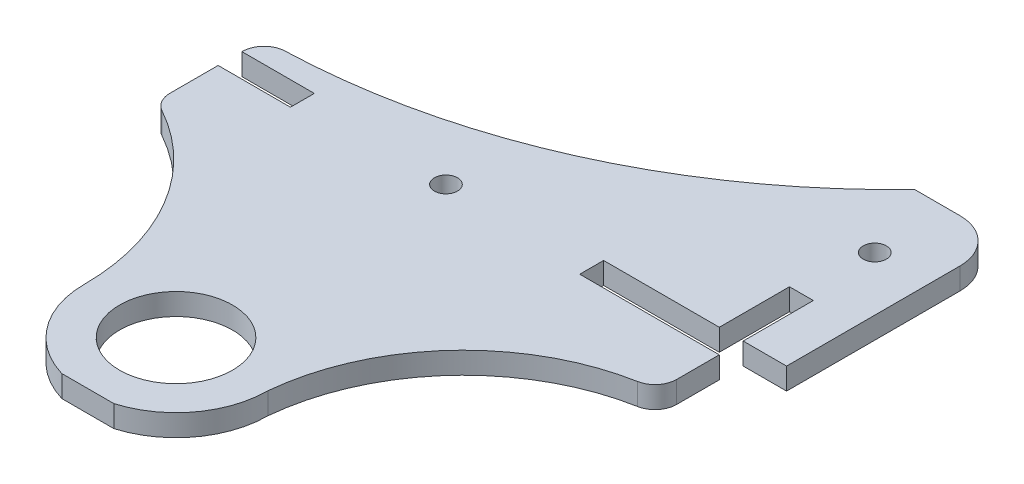
SolidWorks part; units mm, degrees
ref_plane "Alzado" through (0, 0, 0) normal (0, 0, 1) x (1, 0, 0)
ref_plane "Planta" through (0, 0, 0) normal (0, 1, 0) x (1, 0, 0)
ref_plane "Vista lateral" through (0, 0, 0) normal (1, 0, 0) x (0, 0, -1)
sketch "Croquis1" plane through (0, 0, 0) normal (0, 1, 0) x (1, 0, 0)
  line L0 (0, 38.7) -> (69.3, 38.7) construction
  line L1 (0, 0) -> (69.3, 0) construction
  line L2 (0, 0) -> (0, 38.7)
  line L3 (0, 72) -> (69.3, 72)
  line L4 (69.3, 0) -> (69.3, 38.7)
  line L5 (69.3, 51.7) -> (69.3, 72) construction
  line L8 (69.3, 51.7) -> (66, 51.7)
  line L9 (66, 42) -> (66, 51.7)
  line L11 (69.3, 38.7) -> (50, 38.7)
  line L13 (66, 42) -> (50, 42)
  line L14 (50, 38.7) -> (50, 42)
  line L15 (0, 38.7) -> (10, 38.7)
  line L17 (0, 42) -> (10, 42)
  line L18 (10, 38.7) -> (10, 42)
  line L19 (0, 42) -> (0, 72)
  line L20 (69.3, 72) -> (75.3, 72)
  line L21 (69.3, 72) -> (69.3, 51.7) construction
  line L23 (75.3, 72) -> (75.3, 52)
  line L25 (69.3, 51.7) -> (69.3, 42)
  line L26 (69.3, 42) -> (75.3, 42)
  line L27 (75.3, 52) -> (75.3, 42)
  line L28 (0, 0) -> (69.3, 0) construction
  line L29 (0, 0) -> (0, -9)
  line L30 (0, -9) -> (69.3, -9)
  line L31 (69.3, 0) -> (69.3, -9)
  circle A0 centre (30, 40.2) radius 1.6
  circle A1 centre (67.8, 61.7) radius 1.6
  circle A3 centre (29.68, 3.2) radius 7.8109
  dimension "D9" = 3.2
  dimension "D13" = 6
  dimension "D14" = 3.2
  dimension "D18" = 15.6218
  dimension "D2" = 72
  dimension "D3" = 3.3
  dimension "D4" = 13
  dimension "D5" = 16
  dimension "D6" = 3.3
  dimension "D7" = 3.3
  dimension "D8" = 10
  dimension "D10" = 30
  dimension "D11" = 20
  dimension "D12" = 1.5
  dimension "D15" = 1.5
  dimension "D16" = 10
  dimension "D17" = 40
  dimension "D19" = 35.5
  dimension "D20" = 29.68
  dimension "D21" = 30
  dimension "D22" = 9
extrude "Saliente-Extruir10" add sketch "Croquis1" along normal blind 3
sketch "Croquis3" plane through (0, 3, 0) normal (0, 1, 0) x (1, 0, 0)
  line L0 (0, 38.7) -> (0, -9) construction
  line L1 (0, 72) -> (63, 72)
  line L2 (0, 72) -> (0, 45)
  line L5 (10, 38.7) -> (0, 38.7) construction
  line L6 (69.3, -9) -> (69.3, 38.7) construction
  line L7 (69.3, 38.7) -> (50, 38.7) construction
  line L8 (0, -9) -> (69.3, -9) construction
  line L9 (69.3, -9) -> (69.3, 30.2)
  line L10 (0, -9) -> (69.3, -9)
  line L11 (0, 30.2) -> (0, -9)
  arc A0 (42.4, 3.2) -> (69.3, 30.2) centre (72.264, 0.3468) cw
  arc A1 (63, 72) -> (0, 45) centre (0, 132) cw
  arc A4 (16.96, 3.2) -> (42.4, 3.2) centre (29.68, 3.2) ccw
  arc A5 (16.96, 3.2) -> (0, 30.2) centre (-13.04, 3.1823) ccw
  circle M22 centre (67.8, 61.7) radius 1.6
  line M23 (0, 38.7) -> (0, -9)
  line M24 (0, -9) -> (69.3, -9)
  line M25 (69.3, -9) -> (69.3, 38.7)
  line M26 (69.3, 38.7) -> (50, 38.7)
  line M27 (50, 38.7) -> (50, 42)
  line M28 (50, 42) -> (66, 42)
  line M29 (66, 42) -> (66, 51.7)
  line M30 (66, 51.7) -> (69.3, 51.7)
  line M31 (69.3, 51.7) -> (69.3, 42)
  line M32 (69.3, 42) -> (75.3, 42)
  line M33 (75.3, 42) -> (75.3, 72)
  line M34 (75.3, 72) -> (0, 72)
  line M35 (0, 72) -> (0, 42)
  line M36 (0, 42) -> (10, 42)
  line M37 (10, 42) -> (10, 38.7)
  line M38 (10, 38.7) -> (0, 38.7)
  circle M39 centre (30, 40.2) radius 1.6
  dimension "D1" = 30
  dimension "D2" = 25.44
  dimension "D4" = 30
  dimension "D3" = 8.5
  dimension "D5" = 8.5
extrude "Cortar-Extruir2" cut sketch "Croquis3" against normal up to surface (3 mm away) flip side to cut contours A1 M25 M26 M27 M28 M29 M30 M31 M32 M33 M34 M35 M36 M37 M38 M23 M24 M22 M39 region at (38.7096, 3, -32.8066) up to face at (42.4875, 0, -39.7625)
fillet "Redondeo1" radius 6 1 edges at (75.3, 1.5, -72)
fillet "Redondeo2" radius 3 3 edges at (0, 1.5, -45) (69.3, 1.5, -30.2) (0, 1.5, -30.2)
